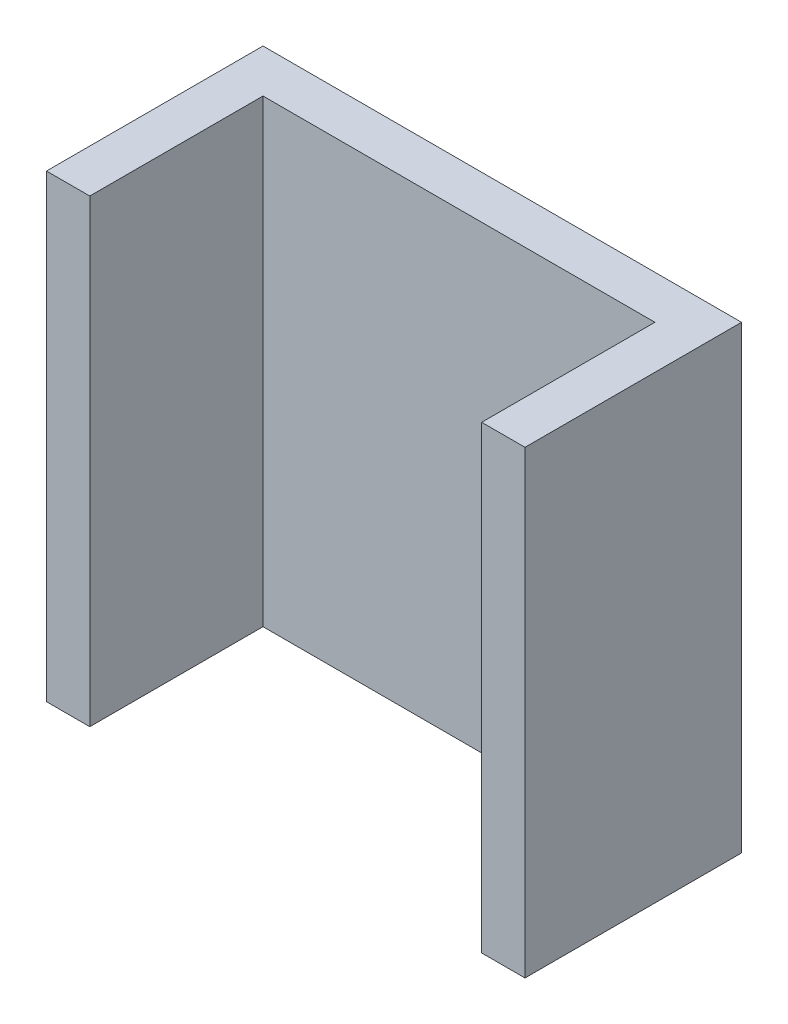
SolidWorks part; units mm, degrees
ref_plane "Front Plane" through (0, 0, 0) normal (0, 0, 1) x (1, 0, 0)
ref_plane "Top Plane" through (0, 0, 0) normal (0, 1, 0) x (1, 0, 0)
ref_plane "Right Plane" through (0, 0, 0) normal (1, 0, 0) x (0, 0, -1)
sketch "Sketch1" plane through (0, 0, 0) normal (1, 0, 0) x (0, 0, -1)
  line L0 (-145, 145) -> (-145, 255)
  line L2 (-145, 0) -> (-145, 145)
  line L3 (-145, 145) -> (0, 145) construction
  line L4 (0, 0) -> (0, 145)
  line L5 (-145, 255) -> (0, 255)
  line L6 (0, 255) -> (0, 145)
  line L7 (0, -145) -> (420.2376, 355.8197) construction
  line L8 (0, -145) -> (-93.2042, -33.9236) construction
  line L9 (94.1529, -32.793) -> (175.1688, -32.793) construction
  line L10 (-93.2042, -33.9236) -> (741.3522, 221.2259) construction
  line L11 (301.5271, 86.7579) -> (438.6224, 86.7579) construction
  line L12 (0, -145) -> (-176.7331, -199.0327) construction
  line L13 (-93.2042, -33.9236) -> (-193.8224, -153.8356) construction
  line L14 (274.6455, 249.3185) -> (274.6455, -80.6815)
  line L15 (274.6455, -80.6815) -> (168.3686, 167.5225)
  arc A0 (0, -145) -> (-145, 0) centre (0, 0) cw
  parabola Q0 (0, 0) -> (300.3031, 267.8046) focus (0, -145) apex (-49.0614, -159.9996)
  parabola Q1 (0, -145) -> (593.7614, 75.583) focus (-93.2042, -33.9236) apex (-147.8987, -99.1059)
  dimension "D1" = 145
  dimension "D2" = 110
  dimension "D3" = 50
  dimension "D4" = 17
  dimension "D5" = 80
  dimension "D6" = 330
  dimension "D7" = 270
sketch "Sketch2" plane through (0, 0, 0) normal (1, 0, 0) x (0, 0, -1)
  line L0 (-145, 145) -> (0, 145) construction
  line L1 (0, 255) -> (0, 145) construction
  line L2 (-145, 255) -> (0, 255) construction
  line L3 (-145, 145) -> (-145, 255) construction
  line L4 (274.6455, -80.6815) -> (168.3686, 167.5225) construction
  line L5 (274.6455, 249.3185) -> (274.6455, -80.6815) construction
  line L6 (0, 0) -> (0, 145) construction
  line L7 (-145, 0) -> (-145, 145) construction
  line L8 (-145, 145) -> (0, 145) construction
  line L9 (0, 255) -> (0, 145)
  line L10 (-145, 255) -> (0, 255)
  line L11 (-145, 145) -> (-145, 255)
  line L12 (274.6455, -80.6815) -> (168.3686, 167.5225)
  line L13 (274.6455, 249.3185) -> (274.6455, -80.6815) construction
  line L14 (0, 0) -> (0, 145)
  line L15 (-145, 0) -> (-145, 145)
  line L16 (-145.6, 0) -> (-145.6, 145)
  line L20 (0.6, 1.8139) -> (0.6, 145)
  line L21 (274.2922, 249.8034) -> (274.6455, 249.3185)
  line L22 (274.6455, -80.6815) -> (274.8642, -81.2403)
  line L23 (168.3686, 167.5225) -> (172.0457, 169.097)
  line L24 (168.3686, 167.5225) -> (274.6455, -80.6815)
  line L25 (172.0457, 169.097) -> (278.3226, -79.1071)
  line L26 (274.6455, -80.6815) -> (278.3226, -79.1071)
  line L27 (0, 145) -> (0.6, 145)
  line L28 (-145, 145) -> (-145.6, 145)
  line L29 (-155, 145) -> (-155, 265)
  line L30 (0.6, 255.6) -> (0.6, 145) construction
  line L31 (-145.6, 255.6) -> (0.6, 255.6) construction
  line L32 (-145.6, 145) -> (-145.6, 255.6) construction
  line L33 (-155, 265) -> (10, 265)
  line L34 (10, 265) -> (10, 145)
  line L35 (-155, 145) -> (-145, 145)
  line L36 (10, 145) -> (0, 145)
  line L38 (0, 145) -> (-145, 145)
  line L39 (0, 145) -> (0, 144.7)
  line L40 (0, 144.7) -> (-145, 144.7)
  line L41 (-145, 145) -> (-145, 144.7)
  arc A0 (-145, 0) -> (0, -145) centre (0, 0) ccw construction
  arc A1 (-145, 0) -> (0, -145) centre (0, 0) ccw
  arc A2 (-145.6, 0) -> (0, -145.6) centre (0, 0) ccw
  parabola Q0 (0, -145) -> (593.7614, 75.583) focus (-93.2042, -33.9236) apex (-147.8987, -99.1059) construction
  parabola Q1 (0, 0) -> (300.3031, 267.8046) focus (0, -145) apex (-49.0614, -159.9996) construction
  parabola Q2 (0, -145) -> (274.6455, -80.6815) focus (-93.2042, -33.9236) apex (-147.8987, -99.1059)
  parabola Q3 (0, 0) -> (274.6455, 249.3185) focus (0, -145) apex (-49.0614, -159.9996)
  spline S0 degree 1 poles (0, -145.6) (274.8642, -81.2403) knots 0 0 1 1 construction
  spline S1 degree 1 poles (0.6, 1.8139) (274.2922, 249.8034) knots 0 0 1 1 construction
  spline S2 degree 3 poles (274.8642, -81.2403) (273.1576, -81.9083) (269.7338, -83.2415) (262.9417, -85.8581) (254.5103, -89.0531) (244.501, -92.7603) (231.2945, -97.5361) (215.05, -103.1917) (195.9774, -109.4761) (177.3259, -115.2579) (153.0186, -122.2971) (123.6866, -129.8396) (90.1715, -136.8804) (63.6442, -141.072) (43.2642, -143.4196) (28.3972, -144.6775) (16.3662, -145.3064) (6.9341, -145.5581) (2.32, -145.6) (0, -145.6) knots 0.50387 0.50387 0.50387 0.50387 0.503942 0.504013 0.504156 0.5043 0.504443 0.504729 0.505015 0.505302 0.505588 0.506161 0.506734 0.507306 0.507593 0.507879 0.508165 0.508308 0.508452 0.508452 0.508452 0.508452
  spline S3 degree 3 poles (0.6, 1.8139) (1.4319, 2.9295) (3.0981, 5.1446) (6.5223, 9.6202) (10.937, 15.2496) (16.4614, 22.0765) (24.1255, 31.2688) (34.2669, 42.9303) (47.3338, 57.1972) (61.2981, 71.7376) (81.1138, 91.4895) (108.1271, 116.8637) (138.1321, 143.1509) (163.9312, 164.7288) (184.1782, 181.1862) (205.3228, 197.9178) (223.6912, 212.0892) (238.8352, 223.5637) (250.4165, 232.2373) (260.2579, 239.5249) (268.2359, 245.3839) (272.2758, 248.3346) (274.2922, 249.8034) knots 0.504877 0.504877 0.504877 0.504877 0.504963 0.505049 0.50522 0.505391 0.505563 0.505905 0.506248 0.50659 0.506933 0.507618 0.508303 0.508646 0.508989 0.509331 0.509674 0.509845 0.510016 0.510188 0.510273 0.510359 0.510359 0.510359 0.510359
  dimension "D2" = 4
  dimension "D4" = 0.3
  dimension "D1" = 0.6
  dimension "D3" = 10
sketch "Sketch3" plane through (0, 0, 0) normal (1, 0, 0) x (0, 0, -1)
  line L0 (274.6455, -80.6815) -> (168.3686, 167.5225) construction
  line L1 (168.3686, 167.5225) -> (172.0457, 169.097) construction
  line L2 (172.0457, 169.097) -> (278.3226, -79.1071) construction
  line L3 (274.6455, -80.6815) -> (278.3226, -79.1071) construction
  line L4 (168.3686, 167.5225) -> (274.6455, -80.6815) construction
  line L5 (0, 255) -> (0, 145) construction
  line L6 (-145, 255) -> (0, 255) construction
  line L7 (-145, 145) -> (-145, 255) construction
  line L8 (-145, 0) -> (-145, 145) construction
  line L9 (-145, 145) -> (-145.6, 145) construction
  line L10 (-145.6, 0) -> (-145.6, 145) construction
  line L11 (274.6455, -80.6815) -> (274.8642, -81.2403) construction
  line L12 (-155, 145) -> (-145, 145) construction
  line L13 (-155, 145) -> (-155, 265) construction
  line L14 (-155, 265) -> (10, 265) construction
  line L15 (10, 265) -> (10, 145) construction
  line L16 (10, 145) -> (0, 145) construction
  line L17 (0, 145) -> (-145, 145) construction
  line L18 (0, 145) -> (0, 144.7) construction
  line L19 (0, 144.7) -> (-145, 144.7) construction
  line L20 (-145, 145) -> (-145, 144.7) construction
  line L21 (0, 0) -> (0, 145) construction
  line L22 (274.2922, 249.8034) -> (274.6455, 249.3185) construction
  line L23 (0.6, 1.8139) -> (0.6, 145) construction
  line L24 (0, 145) -> (0.6, 145) construction
  line L25 (274.6455, -80.6815) -> (168.3686, 167.5225)
  line L26 (168.3686, 167.5225) -> (172.0457, 169.097)
  line L27 (172.0457, 169.097) -> (278.3226, -79.1071)
  line L28 (274.6455, -80.6815) -> (278.3226, -79.1071)
  line L29 (168.3686, 167.5225) -> (274.6455, -80.6815)
  line L30 (0, 255) -> (0, 145)
  line L31 (-145, 255) -> (0, 255)
  line L32 (-145, 145) -> (-145, 255)
  line L33 (-145, 0) -> (-145, 145)
  line L34 (-145, 145) -> (-145.6, 145)
  line L35 (-145.6, 0) -> (-145.6, 145)
  line L36 (274.6455, -80.6815) -> (274.8642, -81.2403)
  line L37 (-155, 145) -> (-145, 145)
  line L38 (-155, 145) -> (-155, 265)
  line L39 (-155, 265) -> (10, 265)
  line L40 (10, 265) -> (10, 145)
  line L41 (10, 145) -> (0, 145)
  line L42 (0, 145) -> (-145, 145)
  line L43 (0, 145) -> (0, 144.7)
  line L44 (0, 144.7) -> (-145, 144.7)
  line L45 (-145, 145) -> (-145, 144.7)
  line L46 (0, 0) -> (0, 145)
  line L47 (274.2922, 249.8034) -> (274.6455, 249.3185)
  line L48 (0.6, 1.8139) -> (0.6, 145)
  line L49 (0, 145) -> (0.6, 145)
  line L50 (-155, 575) -> (-155, 695)
  line L51 (-145, 575) -> (-145, 685)
  line L52 (-155, 695) -> (10, 695)
  line L53 (-145, 685) -> (0, 685)
  line L54 (10, 695) -> (10, 575)
  line L55 (0, 685) -> (0, 575)
  line L56 (10, 575) -> (0, 575)
  line L57 (0.6, 431.8139) -> (0.6, 575)
  line L58 (0, 430) -> (0, 575)
  line L59 (0, 574.7) -> (-145, 574.7)
  line L60 (-145, 430) -> (-145, 575)
  line L61 (-145.6, 430) -> (-145.6, 575)
  line L62 (-155, 575) -> (-145, 575)
  line L63 (274.6455, 349.3185) -> (274.8642, 348.7597)
  line L64 (274.6455, 349.3185) -> (278.3226, 350.8929)
  line L65 (274.6455, 349.3185) -> (168.3686, 597.5225)
  line L66 (172.0457, 599.097) -> (278.3226, 350.8929)
  line L67 (168.3686, 597.5225) -> (172.0457, 599.097)
  line L68 (274.2922, 679.8034) -> (274.6455, 679.3185)
  line L69 (0, 575) -> (-145, 575)
  line L70 (-155, 1005) -> (-155, 1125)
  line L71 (-145, 1005) -> (-145, 1115)
  line L72 (-155, 1125) -> (10, 1125)
  line L73 (-145, 1115) -> (0, 1115)
  line L74 (10, 1125) -> (10, 1005)
  line L75 (0, 1115) -> (0, 1005)
  line L76 (10, 1005) -> (0, 1005)
  line L77 (0.6, 861.8139) -> (0.6, 1005)
  line L78 (0, 860) -> (0, 1005)
  line L79 (0, 1004.7) -> (-145, 1004.7)
  line L80 (-145, 860) -> (-145, 1005)
  line L81 (-145.6, 860) -> (-145.6, 1005)
  line L82 (-155, 1005) -> (-145, 1005)
  line L83 (274.6455, 779.3185) -> (274.8642, 778.7597)
  line L84 (274.6455, 779.3185) -> (278.3226, 780.8929)
  line L85 (274.6455, 779.3185) -> (168.3686, 1027.5225)
  line L86 (172.0457, 1029.097) -> (278.3226, 780.8929)
  line L87 (168.3686, 1027.5225) -> (172.0457, 1029.097)
  line L88 (274.2922, 1109.8034) -> (274.6455, 1109.3185)
  line L89 (0, 1005) -> (-145, 1005)
  arc A0 (-145, 0) -> (0, -145) centre (0, 0) ccw construction
  arc A1 (-145.6, 0) -> (0, -145.6) centre (0, 0) ccw construction
  arc A2 (-145, 0) -> (0, -145) centre (0, 0) ccw
  arc A3 (-145.6, 0) -> (0, -145.6) centre (0, 0) ccw
  arc A4 (-145, 430) -> (0, 285) centre (0, 430) ccw
  arc A5 (-145.6, 430) -> (0, 284.4) centre (0, 430) ccw
  arc A6 (-145, 860) -> (0, 715) centre (0, 860) ccw
  arc A7 (-145.6, 860) -> (0, 714.4) centre (0, 860) ccw
  parabola Q0 (0, -145) -> (274.6455, -80.6815) focus (-93.2042, -33.9236) apex (-147.8987, -99.1059) construction
  parabola Q1 (0, 0) -> (274.6455, 249.3185) focus (0, -145) apex (-49.0614, -159.9996) construction
  parabola Q2 (0, -145) -> (274.6455, -80.6815) focus (-93.2042, -33.9236) apex (-147.8987, -99.1059)
  parabola Q3 (0, 0) -> (274.6455, 249.3185) focus (0, -145) apex (-49.0614, -159.9996)
  parabola Q4 (0, 430) -> (274.6455, 679.3185) focus (0, 285) apex (-49.0614, 270.0004)
  parabola Q5 (0, 285) -> (274.6455, 349.3185) focus (-93.2042, 396.0764) apex (-147.8987, 330.8941)
  parabola Q6 (0, 860) -> (274.6455, 1109.3185) focus (0, 715) apex (-49.0614, 700.0004)
  parabola Q7 (0, 715) -> (274.6455, 779.3185) focus (-93.2042, 826.0764) apex (-147.8987, 760.8941)
  spline S0 degree 3 poles (-2532.6565, -1138.1182) (517.166, 27.2131) (377.0621, -41.8945) (262.9417, -85.8581) (254.5103, -89.0531) (244.501, -92.7603) (231.2945, -97.5361) (215.05, -103.1917) (195.9774, -109.4761) (177.3259, -115.2579) (153.0186, -122.2971) (123.6866, -129.8396) (90.1715, -136.8804) (63.6442, -141.072) (43.2642, -143.4196) (28.3972, -144.6775) (16.3662, -145.3064) (-89.7923, -148.1384) (-144.0863, -112.0401) (-2997.9045, -39.5411) knots 0.499345 0.499345 0.499345 0.499345 0.503942 0.504013 0.504156 0.5043 0.504443 0.504729 0.505015 0.505302 0.505588 0.506161 0.506734 0.507306 0.507593 0.507879 0.508165 0.508308 0.514325 0.514325 0.514325 0.514325 only from (274.8642, -81.2403) to (0, -145.6) construction
  spline S1 degree 3 poles (-1751.4871, -2433.1925) (-55.1342, -100.2952) (-43.2482, -55.4331) (6.5223, 9.6202) (10.937, 15.2496) (16.4614, 22.0765) (24.1255, 31.2688) (34.2669, 42.9303) (47.3338, 57.1972) (61.2981, 71.7376) (81.1138, 91.4895) (108.1271, 116.8637) (138.1321, 143.1509) (163.9312, 164.7288) (184.1782, 181.1862) (205.3228, 197.9178) (223.6912, 212.0892) (238.8352, 223.5637) (250.4165, 232.2373) (260.2579, 239.5249) (377.9568, 325.9622) (533.0374, 426.7515) (-2133.1319, -1539.7711) knots 0.50024 0.50024 0.50024 0.50024 0.504963 0.505049 0.50522 0.505391 0.505563 0.505905 0.506248 0.50659 0.506933 0.507618 0.508303 0.508646 0.508989 0.509331 0.509674 0.509845 0.510016 0.510188 0.510273 0.515071 0.515071 0.515071 0.515071 only from (0.6, 1.8139) to (274.2922, 249.8034) construction
  spline S2 degree 3 poles (274.8642, -81.2403) (273.1576, -81.9083) (269.7338, -83.2415) (262.9417, -85.8581) (254.5103, -89.0531) (244.501, -92.7603) (231.2945, -97.5361) (215.05, -103.1917) (195.9774, -109.4761) (177.3259, -115.2579) (153.0186, -122.2971) (123.6866, -129.8396) (90.1715, -136.8804) (63.6442, -141.072) (43.2642, -143.4196) (28.3972, -144.6775) (16.3662, -145.3064) (6.9341, -145.5581) (2.32, -145.6) (0, -145.6) knots 0.50387 0.50387 0.50387 0.50387 0.503942 0.504013 0.504156 0.5043 0.504443 0.504729 0.505015 0.505302 0.505588 0.506161 0.506734 0.507306 0.507593 0.507879 0.508165 0.508308 0.508452 0.508452 0.508452 0.508452
  spline S3 degree 3 poles (0.6, 1.8139) (1.4319, 2.9295) (3.0981, 5.1446) (6.5223, 9.6202) (10.937, 15.2496) (16.4614, 22.0765) (24.1255, 31.2688) (34.2669, 42.9303) (47.3338, 57.1972) (61.2981, 71.7376) (81.1138, 91.4895) (108.1271, 116.8637) (138.1321, 143.1509) (163.9312, 164.7288) (184.1782, 181.1862) (205.3228, 197.9178) (223.6912, 212.0892) (238.8352, 223.5637) (250.4165, 232.2373) (260.2579, 239.5249) (268.2359, 245.3839) (272.2758, 248.3346) (274.2922, 249.8034) knots 0.504877 0.504877 0.504877 0.504877 0.504963 0.505049 0.50522 0.505391 0.505563 0.505905 0.506248 0.50659 0.506933 0.507618 0.508303 0.508646 0.508989 0.509331 0.509674 0.509845 0.510016 0.510188 0.510273 0.510359 0.510359 0.510359 0.510359
  spline S4 degree 3 poles (0.6, 431.8139) (1.4319, 432.9295) (3.0981, 435.1446) (6.5223, 439.6202) (10.937, 445.2496) (16.4614, 452.0765) (24.1255, 461.2688) (34.2669, 472.9303) (47.3338, 487.1972) (61.2981, 501.7376) (81.1138, 521.4895) (108.1271, 546.8637) (138.1321, 573.1509) (163.9312, 594.7288) (184.1782, 611.1862) (205.3228, 627.9178) (223.6912, 642.0892) (238.8352, 653.5637) (250.4165, 662.2373) (260.2579, 669.5249) (268.2359, 675.3839) (272.2758, 678.3346) (274.2922, 679.8034) knots 0.504877 0.504877 0.504877 0.504877 0.504963 0.505049 0.50522 0.505391 0.505563 0.505905 0.506248 0.50659 0.506933 0.507618 0.508303 0.508646 0.508989 0.509331 0.509674 0.509845 0.510016 0.510188 0.510273 0.510359 0.510359 0.510359 0.510359
  spline S5 degree 3 poles (274.8642, 348.7597) (273.1576, 348.0917) (269.7338, 346.7585) (262.9417, 344.1419) (254.5103, 340.9469) (244.501, 337.2397) (231.2945, 332.4639) (215.05, 326.8083) (195.9774, 320.5239) (177.3259, 314.7421) (153.0186, 307.7029) (123.6866, 300.1604) (90.1715, 293.1196) (63.6442, 288.928) (43.2642, 286.5804) (28.3972, 285.3225) (16.3662, 284.6936) (6.9341, 284.4419) (2.32, 284.4) (0, 284.4) knots 0.50387 0.50387 0.50387 0.50387 0.503942 0.504013 0.504156 0.5043 0.504443 0.504729 0.505015 0.505302 0.505588 0.506161 0.506734 0.507306 0.507593 0.507879 0.508165 0.508308 0.508452 0.508452 0.508452 0.508452
  spline S6 degree 3 poles (0.6, 861.8139) (1.4319, 862.9295) (3.0981, 865.1446) (6.5223, 869.6202) (10.937, 875.2496) (16.4614, 882.0765) (24.1255, 891.2688) (34.2669, 902.9303) (47.3338, 917.1972) (61.2981, 931.7376) (81.1138, 951.4895) (108.1271, 976.8637) (138.1321, 1003.1509) (163.9312, 1024.7288) (184.1782, 1041.1862) (205.3228, 1057.9178) (223.6912, 1072.0892) (238.8352, 1083.5637) (250.4165, 1092.2373) (260.2579, 1099.5249) (268.2359, 1105.3839) (272.2758, 1108.3346) (274.2922, 1109.8034) knots 0.504877 0.504877 0.504877 0.504877 0.504963 0.505049 0.50522 0.505391 0.505563 0.505905 0.506248 0.50659 0.506933 0.507618 0.508303 0.508646 0.508989 0.509331 0.509674 0.509845 0.510016 0.510188 0.510273 0.510359 0.510359 0.510359 0.510359
  spline S7 degree 3 poles (274.8642, 778.7597) (273.1576, 778.0917) (269.7338, 776.7585) (262.9417, 774.1419) (254.5103, 770.9469) (244.501, 767.2397) (231.2945, 762.4639) (215.05, 756.8083) (195.9774, 750.5239) (177.3259, 744.7421) (153.0186, 737.7029) (123.6866, 730.1604) (90.1715, 723.1196) (63.6442, 718.928) (43.2642, 716.5804) (28.3972, 715.3225) (16.3662, 714.6936) (6.9341, 714.4419) (2.32, 714.4) (0, 714.4) knots 0.50387 0.50387 0.50387 0.50387 0.503942 0.504013 0.504156 0.5043 0.504443 0.504729 0.505015 0.505302 0.505588 0.506161 0.506734 0.507306 0.507593 0.507879 0.508165 0.508308 0.508452 0.508452 0.508452 0.508452
  dimension "D1" = 3
extrude "Boss-Extrude1" add sketch "Sketch3" against normal blind 1250 contours S3 L48 L41 L43 L46 Q3 L47 | L41 L40 L39 L38 L37 L34 L32 L31 L30 | L44 L43 L42 L33 | S2 L36 Q2 A2 L33 L34 L35 A3 | L25 L28 L27 L26 | S5 L63 Q5 A4 L60 L62 L61 A5 | L67 L65 L64 L66 | S4 L57 L56 L58 Q4 L68 | L50 L62 L51 L53 L55 L56 L54 L52 | L58 L69 L60 L59 | L87 L85 L84 L86 | S7 L83 Q7 A6 L80 L82 L81 A7 | S6 L77 L76 L78 Q6 L88 | L78 L89 L80 L79 | L70 L82 L71 L73 L75 L76 L74 L72
sketch "Sketch4" plane through (0, 0, 0) normal (1, 0, 0) x (0, 0, -1)
  line L0 (-155, 1125) -> (10, 1125) construction
  line L1 (-180, 1150) -> (278.3226, 1150)
  line L2 (-180, 1150) -> (-180, -170.6)
  line L3 (-180, -170.6) -> (278.3226, -170.6)
  line L4 (278.3226, 1150) -> (278.3226, 1109.3185)
  line L5 (-155, 1005) -> (-155, 1125) construction
  line L6 (274.6455, 1109.3185) -> (278.3226, 1109.3185)
  line L7 (274.6455, 679.3185) -> (278.3226, 679.3185)
  line L8 (274.6455, 249.3185) -> (278.3226, 249.3185)
  line L9 (278.3226, 679.3185) -> (278.3226, 780.8929)
  line L10 (278.3226, -170.6) -> (278.3226, -79.1071)
  line L11 (278.3226, 249.3185) -> (278.3226, 350.8929)
  line L12 (274.6455, 1108.3185) -> (279.3226, 1108.3185)
  line L13 (279.3226, 1151) -> (279.3226, 1108.3185)
  line L14 (-181, 1151) -> (279.3226, 1151)
  line L15 (-181, 1151) -> (-181, -171.6)
  line L16 (-181, -171.6) -> (279.3226, -171.6)
  line L17 (279.3226, -171.6) -> (279.3226, -79.1071)
  line L18 (274.6455, 248.3185) -> (279.3226, 248.3185)
  line L19 (279.3226, 248.3185) -> (279.3226, 350.8929)
  line L20 (274.6455, 678.3185) -> (279.3226, 678.3185)
  line L21 (279.3226, 678.3185) -> (279.3226, 780.8929)
  line L22 (274.6455, 1108.3185) -> (274.6455, 1109.3185)
  line L23 (278.3226, 780.8929) -> (279.3226, 780.8929)
  line L24 (274.6455, 678.3185) -> (274.6455, 679.3185)
  line L25 (279.3226, 350.8929) -> (278.3226, 350.8929)
  line L26 (274.6455, 248.3185) -> (274.6455, 249.3185)
  line L27 (279.3226, -79.1071) -> (278.3226, -79.1071)
  dimension "D1" = 25
  dimension "D2" = 25
  dimension "D3" = 25
  dimension "D4" = 1
extrude "Boss-Extrude2" add sketch "Sketch4" against normal blind 1250 separate body
sketch "Sketch5" plane through (0, 0, 0) normal (1, 0, 0) x (0, 0, -1)
  line L1 (-181, 1151) -> (279.3226, 1151)
  line L2 (-181, 1151) -> (-181, -171.6)
  line L3 (-181, -171.6) -> (279.3226, -171.6)
  line L4 (279.3226, 1151) -> (279.3226, -171.6)
extrude "Boss-Extrude3" add sketch "Sketch5" along normal blind 10 separate body
sketch "Sketch6" plane through (-1250, 0, 0) normal (-1, 0, 0) x (0, 0, 1)
  line L4 (181, 1151) -> (-279.3226, 1151)
  line L5 (-279.3226, 1151) -> (-279.3226, -171.6)
  line L6 (-279.3226, -171.6) -> (181, -171.6)
  line L7 (181, -171.6) -> (181, 1151)
  line L8 (181, 1151) -> (-279.3226, 1151)
  line L9 (-279.3226, 1151) -> (-279.3226, -171.6)
  line L10 (-279.3226, -171.6) -> (181, -171.6)
  line L11 (181, -171.6) -> (181, 1151)
  dimension "D1" = 0
extrude "Boss-Extrude5" add sketch "Sketch6" along normal blind 10 separate body
sketch "Sketch7" plane through (10, 0, 0) normal (1, 0, 0) x (0, 0, -1)
  line L0 (-145, 145) -> (-145, 255) construction
  line L2 (-145, 255) -> (0, 255) construction
  circle A0 centre (-72.5, 200) radius 50
  circle A1 centre (-72.5, -53.7009) radius 50
  circle A2 centre (-72.5, 630) radius 50
  circle A3 centre (-72.5, 376.2991) radius 50
  circle A4 centre (-72.5, 1060) radius 50
  circle A5 centre (-72.5, 806.2991) radius 50
  dimension "D1" = 100
  dimension "D2" = 100
  dimension "D3" = 72.5
  dimension "D4" = 55
  dimension "D5" = 3
sketch "Sketch8" plane through (-1260, 0, 0) normal (-1, 0, 0) x (0, 0, 1)
  circle A1 centre (72.5, 1060) radius 50
  circle A2 centre (72.5, 1060) radius 50
  circle A3 centre (72.5, 376.2991) radius 50
  circle A4 centre (72.5, 376.2991) radius 50
  circle A5 centre (72.5, 630) radius 50
  circle A6 centre (72.5, 630) radius 50
  circle A7 centre (72.5, -53.7009) radius 50
  circle A8 centre (72.5, -53.7009) radius 50
  circle A9 centre (72.5, 200) radius 50
  circle A10 centre (72.5, 200) radius 50
  circle A11 centre (72.5, 806.2991) radius 50
  circle A12 centre (72.5, 806.2991) radius 50
  dimension "D1" = 0
  dimension "D2" = 0
  dimension "D3" = 0
  dimension "D4" = 0
  dimension "D5" = 0
  dimension "D6" = 0
ref_plane "Plane1" through (0, 0, 72.5) normal (0, 0, 1) x (1, 0, 0)
sketch "Sketch10" plane through (-1260, 0, 0) normal (-1, 0, 0) x (0, 0, 1)
  circle A1 centre (72.5, 200) radius 50 construction
  circle A3 centre (72.5, 200) radius 50
sketch "Sketch12" plane through (10, 0, 0) normal (1, 0, 0) x (0, 0, -1)
  circle A0 centre (-72.5, 630) radius 50 construction
  circle A1 centre (-72.5, 630) radius 50
sketch "Sketch14" plane through (10, 0, 0) normal (1, 0, 0) x (0, 0, -1)
  circle A0 centre (-72.5, -53.7009) radius 50 construction
  circle A1 centre (-72.5, -53.7009) radius 50
  circle A2 centre (-72.5, -53.7009) radius 51
  dimension "D1" = 102
ref_plane "Plane2" through (0, 1060, 0) normal (0, 1, 0) x (1, 0, 0)
sketch "Sketch17" plane through (-1260, 0, 0) normal (-1, 0, 0) x (0, 0, 1)
  circle A0 centre (72.5, 1060) radius 50 construction
  circle A1 centre (72.5, 1060) radius 50
  circle A2 centre (72.5, 1060) radius 51
ref_plane "Plane3" through (0, -53.7009, 0) normal (0, 1, 0) x (1, 0, 0)
sketch "Sketch13" plane through (0, 0, 181) normal (0, 0, 1) x (1, 0, 0)
  line L0 (-1250, 1151) -> (0, 1151) construction
  line L1 (-1535, 1651) -> (275, 1651)
  line L2 (-1535, 1651) -> (-1535, -471.6)
  line L3 (-1535, -471.6) -> (275, -471.6)
  line L4 (275, 1651) -> (275, -471.6)
  line L5 (-1250, -171.6) -> (0, -171.6) construction
  line L6 (-1260, -171.6) -> (-1260, 1151) construction
  line L7 (0, 1151) -> (0, -171.6) construction
  dimension "D1" = 500
  dimension "D2" = 300
  dimension "D3" = 275
  dimension "D4" = 275
extrude "Boss-Extrude6" add sketch "Sketch13" along normal blind 200
sketch "Sketch20" plane through (0, 1651, 0) normal (0, 1, 0) x (1, 0, 0)
  line L1 (-1535, -181) -> (-1735, -181)
  line L2 (-1535, -181) -> (-1535, -1181)
  line L3 (-1535, -1181) -> (-1735, -1181)
  line L4 (-1735, -181) -> (-1735, -1181)
  line L5 (275, -181) -> (475, -181)
  line L6 (275, -181) -> (275, -1181)
  line L7 (275, -1181) -> (475, -1181)
  line L8 (475, -181) -> (475, -1181)
  dimension "D1" = 200
  dimension "D2" = 1000
extrude "Boss-Extrude7" add sketch "Sketch20" against normal through all
sketch "Sketch22" plane through (10, 0, 0) normal (1, 0, 0) x (0, 0, -1)
  circle A2 centre (-72.5, 630) radius 50 construction
  circle A3 centre (-72.5, 630) radius 50
sketch "Sketch23" plane through (10, 0, 0) normal (1, 0, 0) x (0, 0, -1)
  circle A2 centre (-72.5, 1060) radius 50 construction
  circle A3 centre (-72.5, 1060) radius 50
sketch "Sketch25" plane through (-1260, 0, 0) normal (-1, 0, 0) x (0, 0, 1)
  circle A0 centre (72.5, 200) radius 50 construction
  circle A1 centre (72.5, 200) radius 50
  circle A3 centre (72.5, 200) radius 51
sketch "Sketch26" plane through (-1260, 0, 0) normal (-1, 0, 0) x (0, 0, 1)
  circle A2 centre (72.5, 806.2991) radius 50 construction
  circle A3 centre (72.5, 806.2991) radius 50
sketch "Sketch29" plane through (0, 0, 72.5) normal (0, 0, 1) x (1, 0, 0)
  line L0 (10, 1060) -> (110, 1060)
  line L1 (110, 630) -> (110, 1060)
  line L2 (110, 630) -> (10, 630)
  dimension "D1" = 100
sketch "Sketch31" plane through (0, 1060, 0) normal (0, 1, 0) x (1, 0, 0)
  line L0 (10, -72.5) -> (215, -72.5)
  line L1 (10, -122.5) -> (10, -22.5) construction
  line L2 (-55, -72.5) -> (55, -72.5) construction
  line L3 (215, -72.5) -> (215, -472.5)
  line L4 (275, -381) -> (275, -1181) construction
  dimension "D1" = 400
  dimension "D2" = 60
sketch "Sketch32" plane through (0, 0, 72.5) normal (0, 0, 1) x (1, 0, 0)
  line L0 (-1260, 200) -> (-1460, 200)
  line L1 (-1460, 200) -> (-1460, 806.2991)
  line L2 (-1260, 806.2991) -> (-1460, 806.2991)
  dimension "D1" = 200
sweep "Sweep13" add profiles "Sketch25" path "Sketch32"
sketch "Sketch34" plane through (0, -53.7009, 0) normal (0, 1, 0) x (1, 0, 0)
  line L0 (215, -72.5) -> (215, -472.5) construction
  line L1 (10, -72.5) -> (215, -72.5) construction
  line L2 (215, -72.5) -> (215, -472.5)
  line L3 (10, -72.5) -> (215, -72.5)
sweep "Sweep14" add profiles "Sketch14" path "Sketch34"
sweep "Sweep-Thin12" add profiles "Sketch12" path "Sketch29" parameters "D1"=1
sweep "Sweep-Thin13" add profiles "Sketch23" path "Sketch31" parameters "D1"=1
sketch "Sketch35" plane through (-1260, 0, 0) normal (-1, 0, 0) x (0, 0, 1)
  line L4 (181, -171.6) -> (181, 1151)
  line L5 (181, 1151) -> (-279.3226, 1151)
  line L6 (-279.3226, 1151) -> (-279.3226, -171.6)
  line L7 (-279.3226, -171.6) -> (181, -171.6)
  line L8 (181, -171.6) -> (181, 1151)
  line L9 (181, 1151) -> (-279.3226, 1151)
  line L10 (-279.3226, 1151) -> (-279.3226, -171.6)
  line L11 (-279.3226, -171.6) -> (181, -171.6)
  circle A0 centre (72.5, 376.2991) radius 50 construction
  circle A1 centre (72.5, 376.2991) radius 50
  dimension "D1" = 0
extrude "Extrude-Thin3" add sketch "Sketch35" along normal up to surface (200 mm away) separate body thin contours A1
